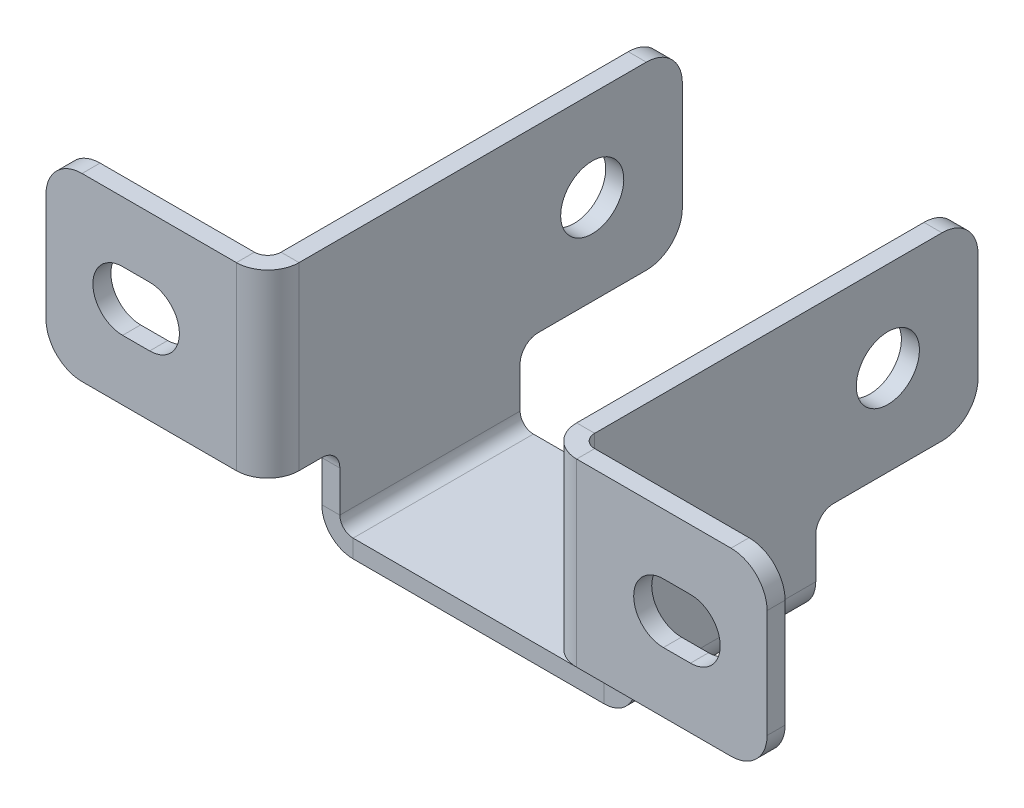
SolidWorks part; units mm, degrees
note: The reader was unsure of these and kept them because the rebuilt part matched: flange length of "Edge-Flange1", "Edge-Flange2".
ref_plane "Front Plane" through (0, 0, 0) normal (0, 0, 1) x (1, 0, 0)
ref_plane "Top Plane" through (0, 0, 0) normal (0, 1, 0) x (1, 0, 0)
ref_plane "Right Plane" through (0, 0, 0) normal (1, 0, 0) x (0, 0, -1)
sketch "Sketch1" plane through (0, 0, 0) normal (0, 1, 0) x (1, 0, 0)
  line L0 (0, 5) -> (0, -5)
  line L1 (0, -5) -> (7.7, -5)
  line L3 (0, 5) -> (7.7, 5)
  line L4 (7.7, -5) -> (7.7, 5)
  point P0 (0, 0)
  dimension "D1" = 7.7
  dimension "D2" = 10
base flange "Base-Flange1" sketch "Sketch1" thickness 1 reverse thickness direction no parameters "D1"=0.7366
edge flange "Edge-Flange1" sketch "Sketch8" flange angle 90 flange length 5 flange position material outside bend radius 0.7366 thickness 1 relief rectangular parameters "D6"=10
sketch "Sketch8" plane through (7.7, 0, 0) normal (-1, 0, 0) x (0, 0, 1)
  line L2 (-5, 0) -> (-5, 4)
  line L3 (-5, 4) -> (5, 4)
  line L4 (5, 4) -> (5, 0)
  line L5 (5, 0) -> (-5, 0) construction
  line L6 (5, 0) -> (-5, 0)
bend "EdgeBend1" bend radius 0.7366 bend angle 90 parameters "D5"=1
sketch "Sketch11" plane through (8.7, 0, 0) normal (1, 0, 0) x (0, 0, -1)
  line L0 (-9, 14) -> (14, 14)
  line L1 (14, 14) -> (14, 4)
  line L2 (14, 4) -> (-9, 4)
  line L3 (-9, 4) -> (-9, 14)
  line L4 (-5, 4) -> (5, 4) construction
  line L5 (-5, 0.7366) -> (-5, 4) construction
  dimension "D1" = 9
  dimension "D2" = 14
  dimension "D3" = 10
  dimension "D4" = 4
base flange "Tab1" sketch "Sketch11" thickness 1 reverse thickness direction no parameters "D1"=0.7366
fillet "Fillet1" radius 1 2 edges at (8.2, 4, -5) (8.2, 4, 5)
fillet "Fillet2" radius 2 2 edges at (8.2, 14, -14) (8.2, 4, -14)
sketch "Sketch15" plane through (8.7, 0, 0) normal (1, 0, 0) x (0, 0, -1)
  line L0 (-9, 9) -> (9, 9) construction
  line L1 (-9, 14) -> (-9, 4) construction
  circle A0 centre (9, 9) radius 1.75
  dimension "D1" = 3.5
  dimension "D2" = 18
extrude "Cut-Extrude1" cut sketch "Sketch15" against normal through all normal cut yes
edge flange "Edge-Flange2" sketch "Sketch18" flange angle 90 flange length 12.3 flange position material inside bend radius 0.7366 thickness 1 relief rectangular parameters "D6"=10
sketch "Sketch18" plane through (8.7, 0, 9) normal (0, 0, -1) x (0, 1, 0)
  line L2 (4, 0) -> (4, 11.3)
  line L3 (4, 11.3) -> (14, 11.3)
  line L4 (14, 11.3) -> (14, 0)
  line L5 (14, 0) -> (4, 0) construction
  line L6 (14, 0) -> (4, 0)
bend "EdgeBend2" bend radius 0.7366 bend angle 90 parameters "D5"=2
sketch "Sketch23" plane through (0, 0, 8) normal (0, 0, -1) x (-1, 0, 0)
  line L0 (-15.75, 9) -> (-14.25, 9) construction
  line L1 (-15.75, 10.65) -> (-14.25, 10.65)
  line L2 (-15.75, 7.35) -> (-14.25, 7.35)
  line L3 (-15.75, 9) -> (-20, 9) construction
  line L4 (-20, 14) -> (-20, 4) construction
  arc A0 (-15.75, 10.65) -> (-15.75, 7.35) centre (-15.75, 9) ccw
  arc A1 (-14.25, 7.35) -> (-14.25, 10.65) centre (-14.25, 9) ccw
  point P2 (-15, 9)
  dimension "D3" = 1.65
  dimension "D1" = 15
  dimension "D2" = 1.5
extrude "Cut-Extrude2" cut sketch "Sketch23" against normal through all normal cut yes
fillet "Fillet3" radius 2 2 edges at (20, 14, 8.5) (20, 4, 8.5)
mirror "Mirror1" about plane through (0, -1, -5) normal (-1, 0, 0) of bodies 107
bend "MirrorBend1" bend radius 0.7366 bend angle 90 parameters "D5"=3
bend "MirrorBend2" bend radius 0.7366 bend angle 90 parameters "D5"=4
sketch "Bend-Lines1" [suppressed] plane through (0, 0, 0) normal (0, 1, 0) x (1, 0, 0)
sketch "Bounding-Box1" [suppressed] plane through (0, 0, 0) normal (0, 1, 0) x (1, 0, 0)
sheet metal parameters "Sheet-Metal1" thickness 1 parameters "D1"=0.7366
flat pattern "Flat-Pattern1" [suppressed]
sketch "Bend-Lines2" plane through (0, 0, 0) normal (0, 1, 0) x (1, 0, 0)
sketch3d "Bounding-Box2" [suppressed]
  line L0 (-7.5, 6, 0) -> (7.5, 6, 0) construction
  line L1 (-7.5, -6, 0) -> (7.5, -6, 0) construction
  line L2 (-7.5, 6, 0) -> (-7.5, -6, 0) construction
  line L3 (7.5, 6, 0) -> (7.5, -6, 0) construction
sheet metal parameters "Sheet-Metal2" thickness 1 parameters "D1"=0.7366
flat pattern "Flat-Pattern1"
sketch "Bend-Lines2" plane through (0, 0, 0) normal (0, 1, 0) x (1, 0, 0)
  line L0 (7.9346, -6) -> (7.9346, 6) construction
  line L1 (7.9346, -6) -> (7.9346, 6) construction
sketch3d "Bounding-Box2" [suppressed]
  line L0 (11.1692, 6, 0) -> (-7.7, 6, 0) construction
  line L1 (11.1692, -6, 0) -> (-7.7, -6, 0) construction
  line L2 (11.1692, 6, 0) -> (11.1692, -6, 0) construction
  line L3 (-7.7, 6, 0) -> (-7.7, -6, 0) construction
bend of the flat pattern "Flatten-<EdgeBend1>1"
sheet metal parameters "Sheet-Metal3" thickness 1 parameters "D1"=0.7366
flat pattern "Flat-Pattern3"
sketch "Bend-Lines3" plane through (0, 0, 0) normal (0, 1, 0) x (1, 0, 0)
  line L0 (7.9346, -6) -> (7.9346, 6) construction
  line L1 (7.9346, -6) -> (7.9346, 6) construction
sketch3d "Bounding-Box3" [suppressed]
  line L0 (18.1692, 15, 0) -> (-7.7, 15, 0) construction
  line L1 (18.1692, -10, 0) -> (-7.7, -10, 0) construction
  line L2 (18.1692, 15, 0) -> (18.1692, -10, 0) construction
  line L3 (-7.7, 15, 0) -> (-7.7, -10, 0) construction
bend of the flat pattern "Flatten-<EdgeBend1>2"
sheet metal parameters "Sheet-Metal4" thickness 1 parameters "D1"=0.7366
flat pattern "Flat-Pattern3"
sketch "Bend-Lines3" plane through (0, 0, 0) normal (0, 1, 0) x (1, 0, 0)
  line L0 (7.9346, -6) -> (7.9346, 6) construction
  line L1 (7.9346, -6) -> (7.9346, 6) construction
sketch3d "Bounding-Box3" [suppressed]
  line L0 (18.1692, 15, 0) -> (-7.7, 15, 0) construction
  line L1 (18.1692, -10, 0) -> (-7.7, -10, 0) construction
  line L2 (18.1692, 15, 0) -> (18.1692, -10, 0) construction
  line L3 (-7.7, 15, 0) -> (-7.7, -10, 0) construction
bend of the flat pattern "Flatten-<EdgeBend1>2"
sheet metal parameters "Sheet-Metal5" thickness 1 parameters "D1"=0.7366
flat pattern "Flat-Pattern3"
sketch "Bend-Lines3" plane through (0, 0, 0) normal (0, 1, 0) x (1, 0, 0)
  line L0 (7.9346, -5) -> (7.9346, 5) construction
  line L1 (7.9346, -5) -> (7.9346, 5) construction
  line L2 (11.1692, -9.2346) -> (18.1692, -9.2346) construction
  line L3 (11.1692, -9.2346) -> (18.1692, -9.2346) construction
sketch3d "Bounding-Box3" [suppressed]
  line L0 (0, -19.7692, 0) -> (0, 15, 0) construction
  line L1 (18.1692, -19.7692, 0) -> (18.1692, 15, 0) construction
  line L2 (0, -19.7692, 0) -> (18.1692, -19.7692, 0) construction
  line L3 (0, 15, 0) -> (18.1692, 15, 0) construction
bend of the flat pattern "Flatten-<EdgeBend1>2"
bend of the flat pattern "Flatten-<EdgeBend2>1"
sheet metal parameters "Sheet-Metal6" thickness 1 parameters "D1"=0.7366
flat pattern "Flat-Pattern6"
sketch "Bend-Lines4" plane through (0, 0, 0) normal (0, 1, 0) x (1, 0, 0)
  line L0 (-22.1692, -8.2346) -> (-12.1692, -8.2346) construction
  line L1 (-7.9346, 5) -> (-7.9346, -5) construction
  line L2 (12.1692, -8.2346) -> (22.1692, -8.2346) construction
  line L3 (7.9346, -5) -> (7.9346, 5) construction
  line L4 (-22.1692, -8.2346) -> (-12.1692, -8.2346) construction
  line L5 (-7.9346, 5) -> (-7.9346, -5) construction
  line L6 (12.1692, -8.2346) -> (22.1692, -8.2346) construction
  line L7 (7.9346, -5) -> (7.9346, 5) construction
sketch3d "Bounding-Box4" [suppressed]
  line L0 (-22.1692, 14, 0) -> (22.1692, 14, 0) construction
  line L1 (-22.1692, -19.7692, 0) -> (22.1693, -19.7692, 0) construction
  line L2 (-22.1692, 14, 0) -> (-22.1692, -19.7692, 0) construction
  line L3 (22.1692, 14, 0) -> (22.1693, -19.7692, 0) construction
bend of the flat pattern "Flatten-<EdgeBend2>2"
bend of the flat pattern "Flatten-<EdgeBend1>3"
bend of the flat pattern "Flatten-<MirrorBend1>1"
bend of the flat pattern "Flatten-<MirrorBend2>1"
sheet metal parameters "Sheet-Metal7" thickness 1 parameters "D1"=0.7366
flat pattern "Flat-Pattern3"
sketch "Bend-Lines3" plane through (0, 0, 0) normal (0, 1, 0) x (1, 0, 0)
  line L0 (7.9346, -5) -> (7.9346, 5) construction
  line L1 (7.9346, -5) -> (7.9346, 5) construction
  line L2 (11.1692, -9.2346) -> (18.1692, -9.2346) construction
  line L3 (11.1692, -9.2346) -> (18.1692, -9.2346) construction
sketch3d "Bounding-Box3" [suppressed]
  line L0 (0, -19.7692, 0) -> (0, 15, 0) construction
  line L1 (18.1692, -19.7692, 0) -> (18.1692, 15, 0) construction
  line L2 (0, -19.7692, 0) -> (18.1692, -19.7692, 0) construction
  line L3 (0, 15, 0) -> (18.1692, 15, 0) construction
bend of the flat pattern "Flatten-<EdgeBend1>2"
bend of the flat pattern "Flatten-<EdgeBend2>1"
